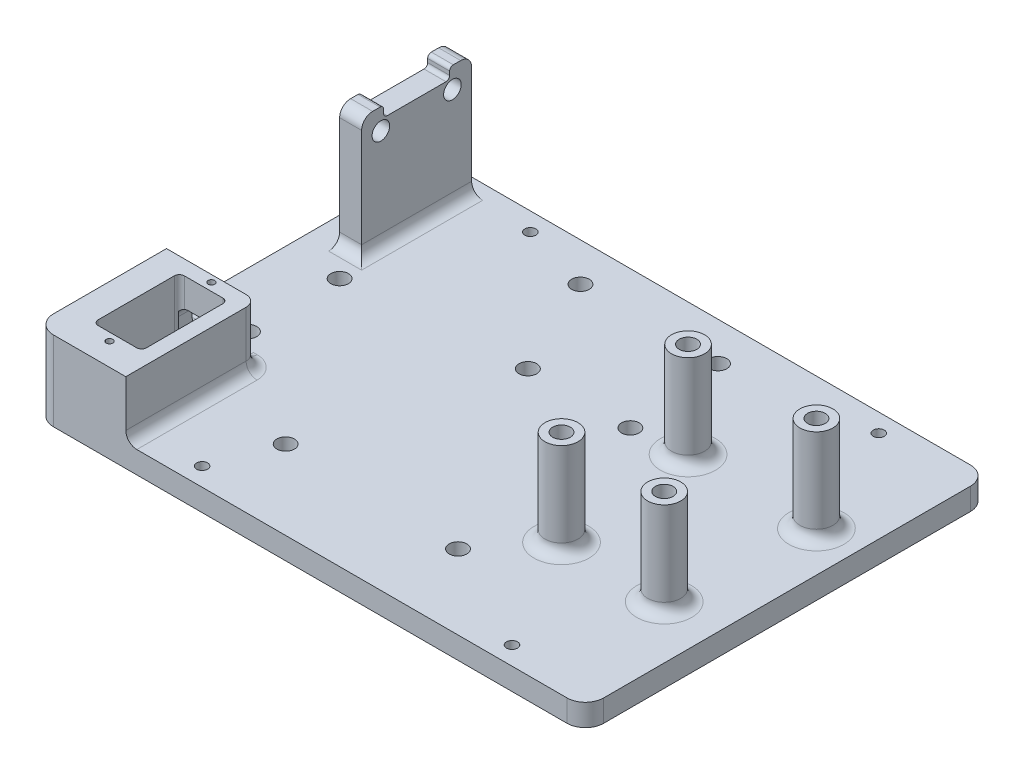
SolidWorks part; units mm, degrees
ref_plane "Front Plane" through (0, 0, 0) normal (0, 0, 1) x (1, 0, 0)
ref_plane "Top Plane" through (0, 0, 0) normal (0, 1, 0) x (1, 0, 0)
ref_plane "Right Plane" through (0, 0, 0) normal (1, 0, 0) x (0, 0, -1)
sketch "Sketch1" plane through (0, 0, 0) normal (0, 1, 0) x (1, 0, 0)
  line L1 (0, 0) -> (150, 0)
  line L2 (0, 0) -> (0, 110)
  line L3 (0, 110) -> (150, 110)
  line L4 (150, 0) -> (150, 110)
  dimension "D1" = 150
  dimension "D2" = 110
extrude "Boss-Extrude1" add sketch "Sketch1" along normal blind 6
hole_wizard "#12 (0.189) Diameter Hole1" positions "Sketch2" profile "Sketch3" hole size "#12" standard "ANSI Inch" end condition up to next
sketch "Sketch2" plane through (0, 6, 0) normal (0, 1, 0) x (1, 0, 0)
  point P0 (89.88, 72.39)
  point P3 (61.94, 72.39)
  point P6 (46.7, 21.59)
  point P9 (94.96, 20.32)
  point P24 (49.16, 99.5)
  point P27 (86.66, 99.5)
  point P30 (15, 68)
  point P33 (15, 43)
sketch "Sketch3" plane through (89.88, 6, -72.39) normal (1, 0, 0) x (0, 0, 1)
  line L0 (0, 0) -> (0, 6)
  line L1 (0, 6) -> (2.4003, 6)
  line L2 (2.4003, 6) -> (2.4003, 0)
  line L5 (2.4003, 0) -> (0, 0)
  line L11 (0, -6.35) -> (0, 107.95) construction
  dimension "Thru Hole Dia." = 4.8006
  dimension "Thru Hole Depth" = 6
sketch "Sketch4" plane through (0, 6, 0) normal (0, 1, 0) x (1, 0, 0)
  line L0 (150, 110) -> (0, 110) construction
  line L1 (7, 106) -> (13, 106)
  line L2 (7, 106) -> (7, 76)
  line L3 (7, 76) -> (13, 76)
  line L4 (13, 106) -> (13, 76)
  line L5 (0, 110) -> (0, 0) construction
  dimension "D1" = 30
  dimension "D2" = 6
  dimension "D3" = 4
  dimension "D4" = 7
extrude "Boss-Extrude2" add sketch "Sketch4" along normal blind 30
ref_plane "Plane1" through (0, 0, -91) normal (0, 0, -1) x (-1, 0, 0)
hole_wizard "#12 (0.189) Diameter Hole2" positions "Sketch5" profile "Sketch6" hole size "#12" standard "ANSI Inch" end condition up to next
sketch "Sketch5" plane through (7, 0, 0) normal (-1, 0, 0) x (0, 0, 1)
  point P0 (-81.25, 33.27)
  point P3 (-100.75, 33.27)
sketch "Sketch6" plane through (7, 33.27, -81.25) normal (0, 1, 0) x (0, 0, 1)
  line L0 (0, 0) -> (0, 6)
  line L1 (0, 6) -> (2.4003, 6)
  line L2 (2.4003, 6) -> (2.4003, 0)
  line L5 (2.4003, 0) -> (0, 0)
  line L11 (0, -6.35) -> (0, 107.95) construction
  dimension "Thru Hole Dia." = 4.8006
  dimension "Thru Hole Depth" = 6
sketch "Sketch7" plane through (0, 36, 0) normal (0, 1, 0) x (1, 0, 0)
  line L0 (13, 76) -> (13, 106) construction
  line L1 (7, 106) -> (13, 106)
  line L2 (7, 106) -> (7, 100)
  line L3 (7, 100) -> (13, 100)
  line L4 (13, 106) -> (13, 100)
  line L6 (7, 76) -> (13, 76)
  line L7 (7, 76) -> (7, 82)
  line L8 (7, 82) -> (13, 82)
  line L9 (13, 76) -> (13, 82)
  dimension "D1" = 6
  dimension "D2" = 6
extrude "Boss-Extrude3" add sketch "Sketch7" along normal blind 3
sketch "Sketch9" plane through (0, 6, 0) normal (0, 1, 0) x (1, 0, 0)
  line L0 (20.2, 9.65) -> (20.2, 30.45) construction
  line L1 (8.85, 8.8) -> (19.35, 8.8) construction
  line L2 (8, 30.45) -> (8, 9.65) construction
  line L3 (19.35, 31.3) -> (8.85, 31.3) construction
  line L4 (20.2, 9.65) -> (20.2, 30.45) construction
  line L5 (8.85, 8.8) -> (19.35, 8.8) construction
  line L6 (8, 30.45) -> (8, 9.65) construction
  line L7 (19.35, 31.3) -> (8.85, 31.3) construction
  line L8 (20.7, 9.65) -> (20.7, 30.45)
  line L9 (19.35, 31.8) -> (8.85, 31.8)
  line L10 (7.5, 30.45) -> (7.5, 9.65)
  line L11 (8.85, 8.3) -> (19.35, 8.3)
  line L13 (0, 0) -> (24.7, 0)
  line L14 (0, 0) -> (0, 35.8)
  line L15 (0, 35.8) -> (24.7, 35.8)
  line L16 (24.7, 0) -> (24.7, 35.8)
  arc A0 (20.2, 30.45) -> (19.35, 31.3) centre (19.35, 30.45) ccw construction
  arc A1 (19.35, 8.8) -> (20.2, 9.65) centre (19.35, 9.65) ccw construction
  arc A2 (8, 9.65) -> (8.85, 8.8) centre (8.85, 9.65) ccw construction
  arc A3 (8.85, 31.3) -> (8, 30.45) centre (8.85, 30.45) ccw construction
  arc A4 (20.2, 30.45) -> (19.35, 31.3) centre (19.35, 30.45) ccw construction
  arc A5 (19.35, 8.8) -> (20.2, 9.65) centre (19.35, 9.65) ccw construction
  arc A6 (8, 9.65) -> (8.85, 8.8) centre (8.85, 9.65) ccw construction
  arc A7 (8.85, 31.3) -> (8, 30.45) centre (8.85, 30.45) ccw construction
  arc A8 (20.7, 30.45) -> (19.35, 31.8) centre (19.35, 30.45) ccw
  arc A9 (8.85, 31.8) -> (7.5, 30.45) centre (8.85, 30.45) ccw
  arc A10 (7.5, 9.65) -> (8.85, 8.3) centre (8.85, 9.65) ccw
  arc A11 (19.35, 8.3) -> (20.7, 9.65) centre (19.35, 9.65) ccw
  dimension "D2" = 4
  dimension "D3" = 4
  dimension "D1" = 0.5
extrude "Boss-Extrude4" add sketch "Sketch9" along normal blind 15.7
sketch "Sketch10" plane through (0, 0, -35.8) normal (0, 0, -1) x (-1, 0, 0)
  line L0 (-7, 39) -> (-7, 6) construction
  line L1 (-20.7, 6) -> (-7, 6)
  line L2 (-20.7, 6) -> (-20.7, 14)
  line L3 (-20.7, 14) -> (-7, 14)
  line L4 (-7, 6) -> (-7, 14)
  dimension "D1" = 8
extrude "Cut-Extrude1" cut sketch "Sketch10" against normal up to surface (4.5 mm away)
sketch "Sketch11" plane through (0, 6, 0) normal (0, 1, 0) x (1, 0, 0)
  arc A0 (108.75, 36) -> (106.25, 36) centre (107.5, 36) ccw construction
  arc A1 (136.75, 36) -> (134.25, 36) centre (135.5, 36) ccw construction
  arc A2 (140.25, 74) -> (137.75, 74) centre (139, 74) ccw construction
  arc A3 (105.25, 74) -> (102.75, 74) centre (104, 74) ccw construction
  arc A4 (108.75, 36) -> (106.25, 36) centre (107.5, 36) ccw construction
  arc A5 (136.75, 36) -> (134.25, 36) centre (135.5, 36) ccw construction
  arc A6 (140.25, 74) -> (137.75, 74) centre (139, 74) ccw construction
  arc A7 (105.25, 74) -> (102.75, 74) centre (104, 74) ccw construction
  circle A8 centre (104, 74) radius 4.5
  circle A9 centre (139, 74) radius 4.5
  circle A10 centre (107.5, 36) radius 4.5
  circle A11 centre (135.5, 36) radius 4.5
  dimension "D1" = 9
extrude "Boss-Extrude5" add sketch "Sketch11" along normal blind 26
hole_wizard "#12 (0.189) Diameter Hole3" positions "Sketch12" profile "Sketch13" hole size "#12" standard "ANSI Inch" end condition up to next
sketch "Sketch12" plane through (0, 32, 0) normal (0, 1, 0) x (1, 0, 0)
  point P0 (104, 74)
  point P3 (139, 74)
  point P6 (107.5, 36)
  point P9 (135.5, 36)
sketch "Sketch13" plane through (104, 32, -74) normal (1, 0, 0) x (0, 0, 1)
  line L0 (0, 0) -> (0, 32)
  line L1 (0, 32) -> (2.4003, 32)
  line L2 (2.4003, 32) -> (2.4003, 0)
  line L5 (2.4003, 0) -> (0, 0)
  line L11 (0, -6.35) -> (0, 107.95) construction
  dimension "Thru Hole Dia." = 4.8006
  dimension "Thru Hole Depth" = 32
fillet "Fillet3" radius 5 4 edges at (150, 3, -110) (150, 3, 0) (0, 10.85, 0) (0, 3, -110)
fillet "Fillet4" radius 3 14 edges at (107.5, 6, -40.5) (10, 39, -76) (10, 39, -106) (10, 6, -76) (13, 6, -91) (20.7, 14, -33.55) (7, 14, -33.55) (24.7, 13.85, -35.8) (22.7, 6, -35.8) (3.5, 6, -35.8) (24.7, 6, -17.9) (104, 6, -78.5) (139, 6, -78.5) (135.5, 6, -40.5)
fillet "Fillet5" radius 1 4 edges at (10, 36, -100) (10, 39, -100) (10, 39, -82) (10, 36, -82)
hole_wizard "Ø3.0mm Dowel Hole1" positions "Sketch14" profile "Sketch15" hole size "Ø3.0" standard "ANSI Metric" end condition up to next
sketch "Sketch14" plane through (0, 6, 0) normal (0, 1, 0) x (1, 0, 0)
  line L0 (145, 110) -> (5, 110) construction
  line L1 (150, 5) -> (150, 105) construction
  line L3 (27.7, 0) -> (145, 0) construction
  line L4 (0, 105) -> (0, 38.8) construction
  line L6 (35.5, 0) -> (35.5, 38.65) construction
  point P0 (30, 105)
  point P2 (40.5, 5)
  point P4 (125, 5)
  point P6 (125, 105)
  point P22 (0, 0)
  point P25 (0, 0)
  point P26 (0, 0)
  dimension "D1" = 5
  dimension "D2" = 25
  dimension "D3" = 5
  dimension "D4" = 5
  dimension "D5" = 30
sketch "Sketch15" plane through (30, 6, -105) normal (1, 0, 0) x (0, 0, 1)
  line L0 (0, 0) -> (0, 6)
  line L1 (0, 6) -> (1.5, 6)
  line L2 (1.5, 6) -> (1.5, 0)
  line L5 (1.5, 0) -> (0, 0)
  line L11 (0, -6.35) -> (0, 107.95) construction
  dimension "Thru Hole Dia." = 3
  dimension "Thru Hole Depth" = 6
sketch "Sketch16" plane through (0, 21.7, 0) normal (0, 1, 0) x (1, 0, 0)
  circle A0 centre (14.1, 6.15) radius 0.9
  circle A1 centre (14.1, 33.95) radius 0.9
  dimension "D1" = 1.8
  dimension "D2" = 1.8
extrude "Cut-Extrude2" cut sketch "Sketch16" against normal blind 5
